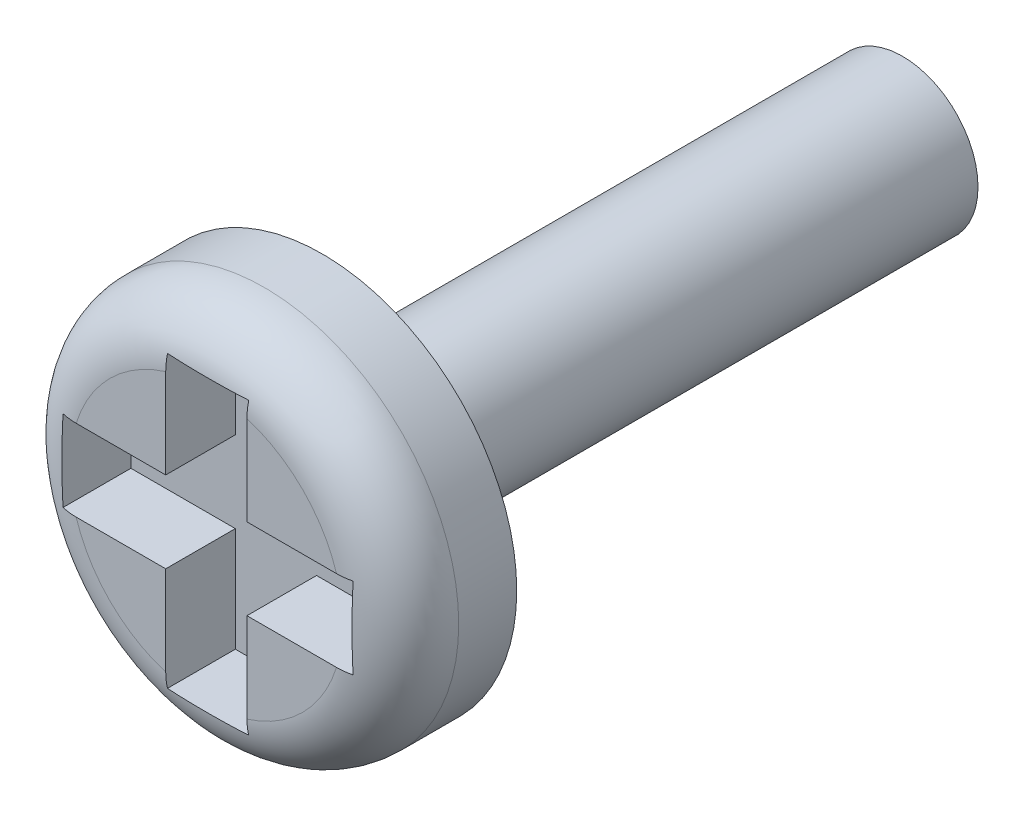
SolidWorks part; units mm, degrees
ref_plane "Alzado" through (0, 0, 0) normal (0, 0, 1) x (1, 0, 0)
ref_plane "Planta" through (0, 0, 0) normal (0, 1, 0) x (1, 0, 0)
ref_plane "Vista lateral" through (0, 0, 0) normal (1, 0, 0) x (0, 0, -1)
sketch "Croquis1" plane through (0, 0, 0) normal (0, 0, 1) x (1, 0, 0)
  circle A0 centre (0, 0) radius 0.65
  dimension "D1" = 1.3
extrude "Saliente-Extruir1" add sketch "Croquis1" along normal blind 5
sketch "Croquis2" plane through (0, 0, 5) normal (0, 0, 1) x (1, 0, 0)
  circle A0 centre (0, 0) radius 1.675
  dimension "D1" = 3.35
extrude "Saliente-Extruir2" add sketch "Croquis2" along normal blind 1
sketch "Croquis3" plane through (0, 0, 6) normal (0, 0, 1) x (1, 0, 0)
  line L0 (0.35, 0.35) -> (1.25, 0.35)
  line L1 (-0.35, -1.25) -> (0.35, -1.25)
  line L2 (-0.35, -1.25) -> (-0.35, -0.35)
  line L3 (-0.35, 1.25) -> (0.35, 1.25)
  line L4 (0.35, -1.25) -> (0.35, -0.35)
  line L7 (-1.25, -0.35) -> (-0.35, -0.35)
  line L8 (-1.25, -0.35) -> (-1.25, 0.35)
  line L9 (-1.25, 0.35) -> (-0.35, 0.35)
  line L10 (1.25, -0.35) -> (1.25, 0.35)
  line L13 (-0.35, 0.35) -> (-0.35, 1.25)
  line L15 (0.35, 0.35) -> (0.35, 1.25)
  line L16 (0.35, -0.35) -> (1.25, -0.35)
  point P0 (0, 0)
  point P6 (0, 0)
  dimension "D1" = 2.5
  dimension "D2" = 2.5
  dimension "D3" = 0.7
  dimension "D4" = 0.7
extrude "Cortar-Extruir1" cut sketch "Croquis3" against normal blind 0.6
fillet "Redondeo1" radius 0.5 1 edges at (1.675, 0, 6)
